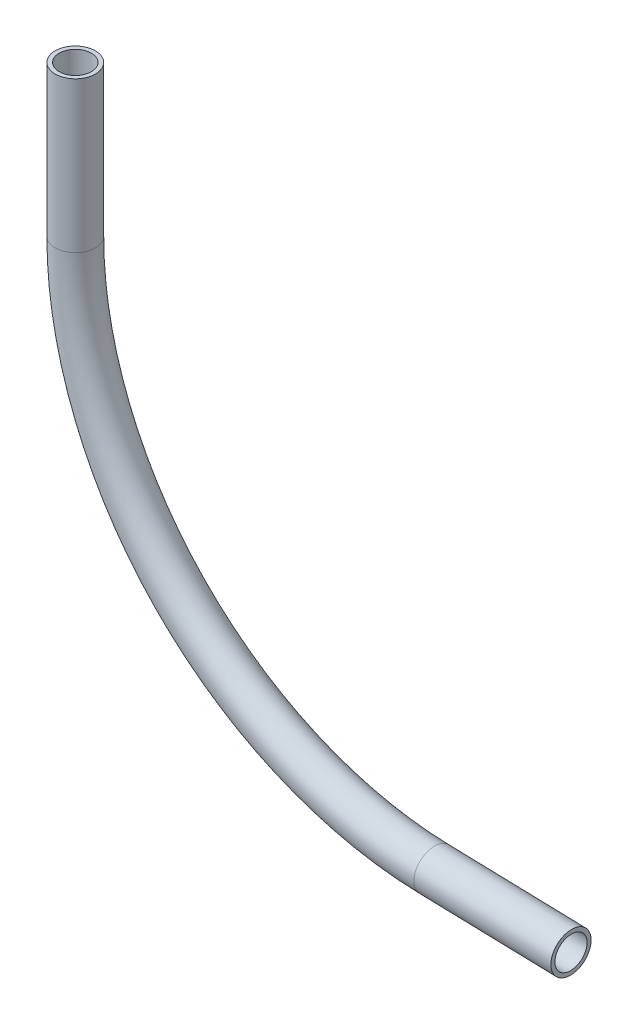
SolidWorks part; units mm, degrees
ref_plane "Front Plane" through (0, 0, 0) normal (0, 0, 1) x (1, 0, 0)
ref_plane "Top Plane" through (0, 0, 0) normal (0, 1, 0) x (1, 0, 0)
ref_plane "Right Plane" through (0, 0, 0) normal (1, 0, 0) x (0, 0, -1)
sketch "Sketch3" plane through (0, 0, 0) normal (0, 0, 1) x (1, 0, 0)
  line L0 (0, 81.8399) -> (0, 110.3709)
  line L1 (67.9642, 12.0154) -> (93.9265, 11.3142)
  arc A0 (0, 81.8399) -> (67.9642, 12.0154) centre (69.85, 81.8399) ccw
  point P6 (0, 13.8509)
  dimension "D4" = 69.85
  dimension "D2" = 93.9607
  dimension "D3" = 96.52
ref_plane "Plane2" through (0, 110.3709, 0) normal (0, 1, 0) x (-1, 0, 0)
sketch "Sketch4" plane through (0, 110.3709, 0) normal (0, 1, 0) x (-1, 0, 0)
  circle A0 centre (0, 0) radius 3.81
  circle A1 centre (0, 0) radius 3.048
  dimension "D1" = 7.62
  dimension "D2" = 6.096
extrude "Boss-Extrude1" add sketch "Sketch4" against normal blind 2.54
sweep "Sweep2" add profiles "Sketch4<3>" path "Sketch3"
sketch "Sketch4<3>" plane through (0, 110.3709, 0) normal (0, 1, 0) x (-1, 0, 0) same geometry as "Sketch4"
sketch "Sketch5" plane through (0, 0, 0) normal (0, 0, 1) x (1, 0, 0)
  line L0 (-3.81, 107.8191) -> (3.81, 107.8191)
  line L1 (-3.81, 110.3709) -> (-3.81, 81.8399) construction
  line L2 (3.81, 81.8399) -> (3.81, 110.3709) construction
